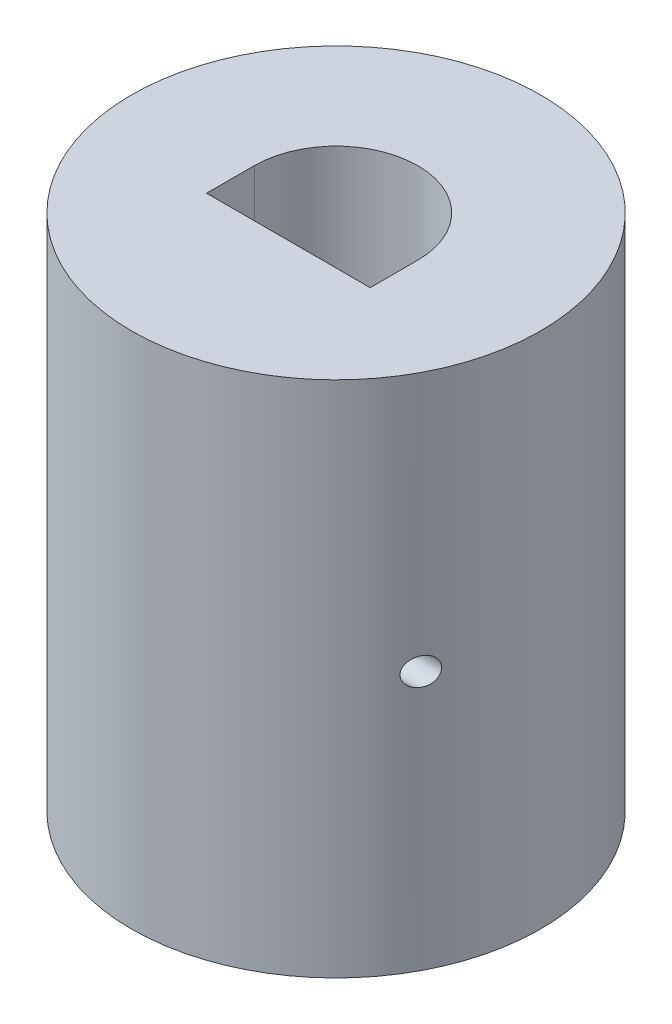
SolidWorks part; units mm, degrees
ref_plane "Front Plane" through (0, 0, 0) normal (0, 0, 1) x (1, 0, 0)
ref_plane "Top Plane" through (0, 0, 0) normal (0, 1, 0) x (1, 0, 0)
ref_plane "Right Plane" through (0, 0, 0) normal (1, 0, 0) x (0, 0, -1)
sketch "Sketch1" plane through (0, 0, 0) normal (0, 1, 0) x (1, 0, 0)
  circle A0 centre (0, 0) radius 7.5
  dimension "D1" = 15
extrude "Boss-Extrude1" add sketch "Sketch1" along normal blind 19
sketch "Sketch2" plane through (0, 0, 0) normal (0, -1, 0) x (1, 0, 0)
  line L0 (-2.4367, 1.75) -> (2.4367, 1.75)
  line L1 (0, 3) -> (0, 1.75) construction
  line L2 (-3, 0) -> (-3, 1.75)
  line L3 (-3, 1.75) -> (-2.4367, 1.75)
  line L4 (2.4367, 1.75) -> (3, 1.75)
  line L5 (3, 1.75) -> (3, 0)
  arc A0 (-3, 0) -> (3, 0) centre (0, 0) ccw
  arc A1 (2.4367, 1.75) -> (-2.4367, 1.75) centre (0, 0) ccw
  dimension "D1" = 6
  dimension "D2" = 4.75
extrude "Cut-Extrude1" cut sketch "Sketch2" against normal through all contours L0 A0 region at (0, 0, -0.3577)
sketch "Sketch3" plane through (0, 0, 0) normal (1, 0, 0) x (0, 0, -1)
  line L0 (7.5, 9.5) -> (-3.5, 9.5) construction
  line L1 (7.5, 0) -> (7.5, 19) construction
  line L2 (7.5, 0) -> (7.5, 19) construction
  circle A0 centre (-3.5, 9.5) radius 0.5
  dimension "D1" = 3.5
  dimension "D2" = 1
extrude "Cut-Extrude2" cut sketch "Sketch3" against normal through all both and the other way through all
sketch "Sketch4" plane through (0, 0, 0) normal (0, 0, 1) x (1, 0, 0)
  line L0 (7.5, 19) -> (10, 19)
  line L1 (10, 19) -> (10, 18)
  line L2 (10, 18) -> (7.5, 13.6699)
  line L3 (7.5, 0) -> (7.5, 19) construction
  line L4 (7.5, 13.6699) -> (7.5, 19)
  line L5 (7.5, 5.3301) -> (10, 1)
  line L6 (10, 1) -> (10, 0)
  line L7 (10, 0) -> (7.5, 0)
  line L8 (7.5, 0) -> (7.5, 5.3301)
  line L9 (0, 0) -> (0, 19) construction
  line L10 (-3, 19) -> (3, 19) construction
  dimension "D1" = 60
  dimension "D2" = 1
  dimension "D3" = 10
revolve "Revolve1" [suppressed] add sketch "Sketch4" angle 360 about L9
